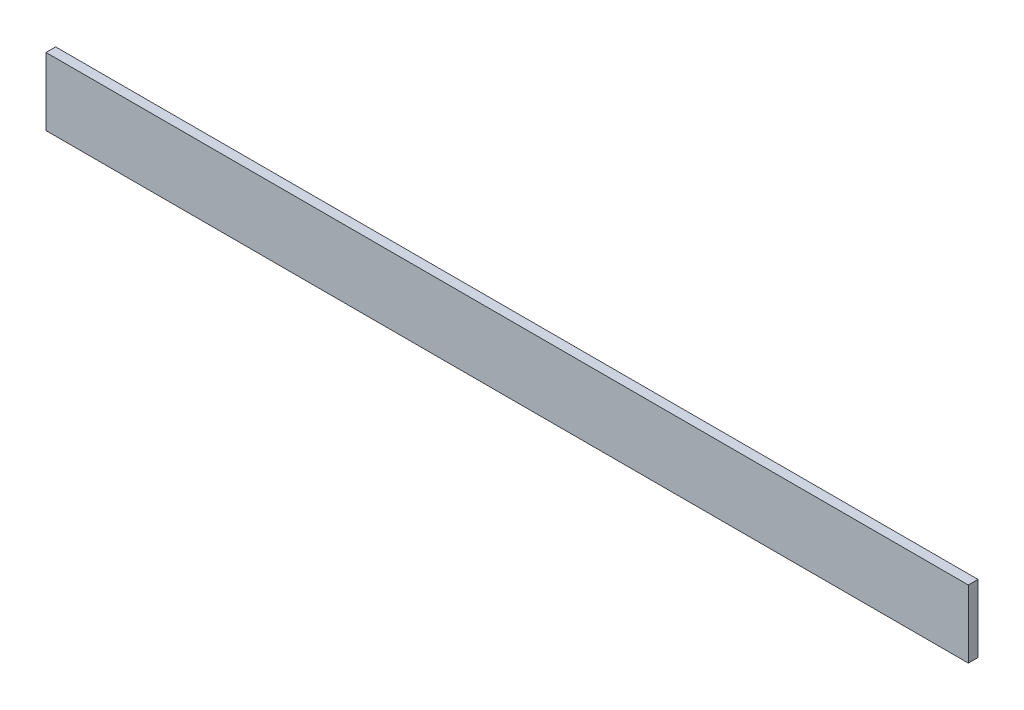
SolidWorks part; units mm, degrees
material "1.4016 (X6Cr17)"
ref_plane "前视基准面" through (0, 0, 0) normal (0, 0, 1) x (1, 0, 0)
ref_plane "上视基准面" through (0, 0, 0) normal (0, 1, 0) x (1, 0, 0)
ref_plane "右视基准面" through (0, 0, 0) normal (1, 0, 0) x (0, 0, -1)
sketch "草图2" plane through (0, 0, 0) normal (0, 0, 1) x (1, 0, 0)
  line L1 (-477, 35) -> (477, 35)
  line L2 (-477, 35) -> (-477, -35)
  line L3 (-477, -35) -> (477, -35)
  line L4 (477, 35) -> (477, -35)
  line L5 (-477, 35) -> (477, -35) construction
  line L6 (-477, -35) -> (477, 35) construction
  point P0 (0, 0)
  dimension "D1" = 954
  dimension "D2" = 70
base flange "基体-法兰1" sketch "草图2" thickness 10 reverse thickness direction no parameters "D1"=2
ref_plane "基准面1" through (0, 0, -5) normal (0, 0, 1) x (1, 0, 0)
sketch "折弯-线1" plane through (0, 0, 0) normal (0, 1, 0) x (1, 0, 0)
sketch "边界框1" plane through (0, 0, 0) normal (0, 1, 0) x (1, 0, 0)
sheet metal parameters "钣金(1)" thickness 10 parameters "D1"=2
flat pattern "平板型式(1)" [suppressed]
sketch "折弯-线2" plane through (0, 0, 0) normal (0, 1, 0) x (1, 0, 0)
sketch "边界框2" [suppressed] plane through (0, 0, 0) normal (0, 1, 0) x (1, 0, 0)
